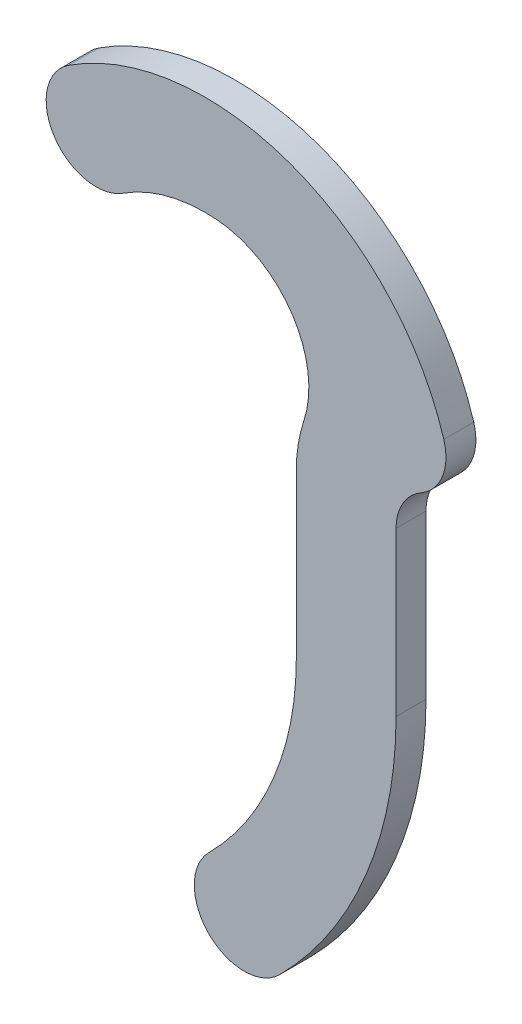
SolidWorks part; units mm, degrees
ref_plane "Plan de face" through (0, 0, 0) normal (0, 0, 1) x (1, 0, 0)
ref_plane "Plan de dessus" through (0, 0, 0) normal (0, 1, 0) x (1, 0, 0)
ref_plane "Plan de droite" through (0, 0, 0) normal (1, 0, 0) x (0, 0, -1)
sketch "Esquisse1" plane through (0, 0, 0) normal (0, 0, 1) x (1, 0, 0)
  line L0 (-10, -25) -> (-10, -8.6603)
  line L2 (0, -8.6603) -> (0, -25)
  arc A0 (0, -25) -> (-11.6846, -53.2531) centre (-40, -25) cw
  arc A1 (-11.6846, -53.2531) -> (-18.7635, -46.1899) centre (-15.2241, -49.7215) cw
  arc A2 (-10, -25) -> (-18.7635, -46.1899) centre (-40, -25) cw
  arc A3 (-2.5, 4.3301) -> (2.5, -4.3301) centre (0, 0) cw
  arc A4 (-2.5, 4.3301) -> (-10, -8.6603) centre (5, -8.6603) ccw
  arc A5 (2.5, -4.3301) -> (0, -8.6603) centre (5, -8.6603) ccw
  dimension "D3" = 40
  dimension "D2" = 5
  dimension "D4" = 25
  dimension "D5" = 52
extrude "Boss.-Extru.1" add sketch "Esquisse1" along normal mid plane 3
sketch "Esquisse4" plane through (0, 0, 1.5) normal (0, 0, 1) x (1, 0, 0)
  line L0 (0, 0) -> (-30.0702, 10.9446) construction
  line L1 (0, 0) -> (0, -17.0518) construction
  arc A0 (-27.3375, 6.7575) -> (-32.8029, 15.1318) centre (-30.0702, 10.9446) cw
  arc A1 (-27.3375, 6.7575) -> (-4.7848, -1.451) centre (-19.1393, -5.804) cw
  arc A2 (-4.7848, -1.451) -> (4.7848, 1.451) centre (0, 0) ccw
  arc A3 (4.7848, 1.451) -> (-32.8029, 15.1318) centre (-19.1393, -5.804) ccw
  dimension "D1" = 5
  dimension "D3" = 15
  dimension "D2" = 32
  dimension "D4" = 110
extrude "Boss.-Extru.2" add sketch "Esquisse4" against normal up to surface (3 mm away) up to face at (-5.8825, -21.0617, -1.5)
sketch "Esquisse2" plane through (0, 0, -1.5) normal (0, 0, -1) x (-1, 0, 0)
  circle A0 centre (0, 0) radius 2.5
  dimension "D1" = 5
extrude "Enlèv. mat.-Extru.3" cut sketch "Esquisse2" against normal blind 2
fillet "Congé1" radius 10 1 edges at (-6.0367, 1.4981, 0)
